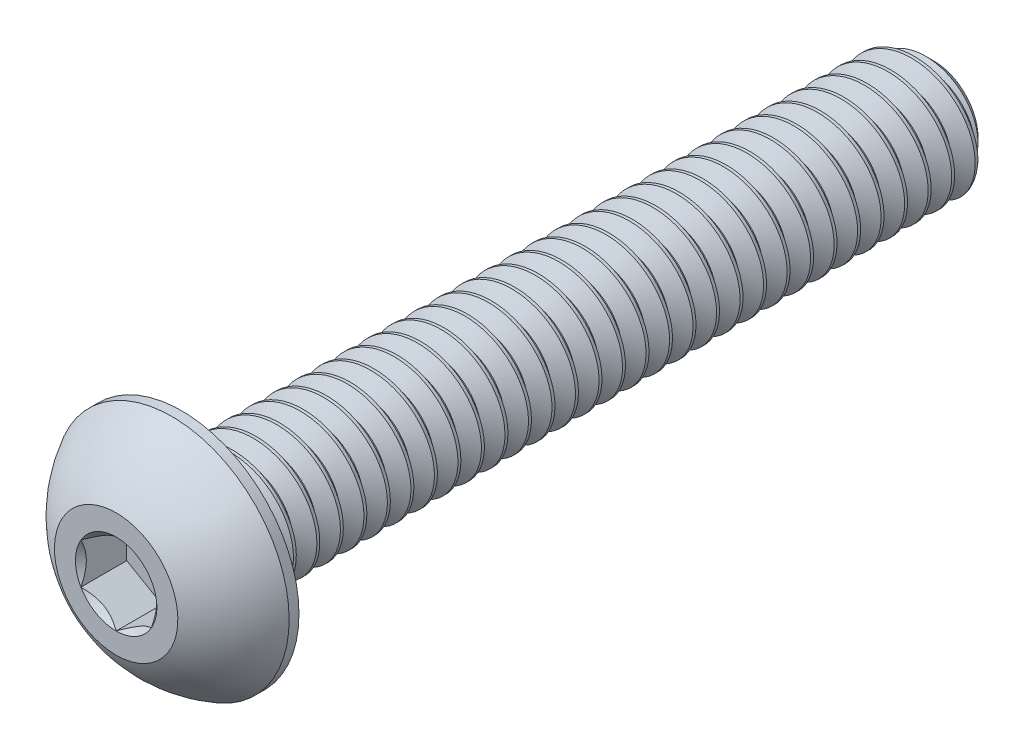
SolidWorks part; units mm, degrees
ref_plane "Front" through (0, 0, 0) normal (0, 0, 1) x (1, 0, 0)
ref_plane "Top" through (0, 0, 0) normal (0, 1, 0) x (1, 0, 0)
ref_plane "Right" through (0, 0, 0) normal (1, 0, 0) x (0, 0, -1)
sketch "Sketch1" plane through (0, 0, 0) normal (1, 0, 0) x (0, 0, -1)
  line L2 (2.2098, 2.0828) -> (27.6098, 2.0828)
  line L3 (27.6098, 2.0828) -> (27.6098, 0)
  line L4 (27.6098, 0) -> (2.2098, 0)
  line L6 (1.8783, 3.9624) -> (2.2098, 3.9624) construction
  line L7 (27.6098, 2.0828) -> (27.6098, -2.0828) construction
  line L8 (0, 0) -> (2.2098, 0) construction
  line L9 (2.2098, 3.9624) -> (2.2098, -3.9624) construction
  line L11 (2.2098, 2.0828) -> (2.2098, 0)
  line L13 (0, 1.1906) -> (0, -1.1906) construction
  line L14 (0, 1.1906) -> (0, 2.0828) construction
  arc A3 (0, 2.0828) -> (1.8783, 3.9624) centre (3.9638, 0) cw construction
  dimension "D1" = 0.3315
  dimension "Head Ht" = 2.2098
  dimension "Head Dia" = 7.9248
  dimension "Dia" = 4.1656
  dimension "Lg" = 25.4
  dimension "Hex" = 2.3813
revolve "Revolve1" add sketch "Sketch1" angle 360 mid plane about L4
sketch "Sketch3" plane through (0, 0, -27.6098) normal (0, 0, -1) x (-1, 0, 0)
  circle A0 centre (0, 0) radius 2.0828
curve "Helix/Spiral1" pitch 0.7937 height 27.6098 turns 34.784
sketch "Sketch2" plane through (0, 0, 0) normal (1, 0, 0) x (0, 0, -1)
  line L0 (27.6098, 2.0828) -> (28.3043, 2.0828)
  line L1 (28.3043, 2.0828) -> (28.0067, 1.5672)
  line L2 (28.0067, 1.5672) -> (27.9075, 1.5672)
  line L3 (27.9075, 1.5672) -> (27.6098, 2.0828)
  line L4 (27.7586, 1.825) -> (28.1555, 1.825) construction
  dimension "D1" = 60
  dimension "D2" = 0.0992
  dimension "D3" = 0.3969
chamfer "Chamfer1" distance 0.5953 angle 45 1 edges at (0, 2.0828, -27.6098)
sweep "Cut-Sweep1" cut profiles "Sketch2" path "Helix/Spiral1"
sketch "Sketch7" plane through (0, 0, 0) normal (1, 0, 0) x (0, 0, -1)
  line L6 (1.8783, 3.9624) -> (2.2098, 3.9624) construction
  line L8 (0, 0) -> (2.2098, 0) construction
  line L11 (2.2098, 3.9624) -> (2.2098, -3.9624) construction
  line L12 (1.8783, 3.9624) -> (2.2098, 3.9624)
  line L13 (0, 0) -> (2.2098, 0)
  line L14 (0, 1.1906) -> (0, -1.1906) construction
  line L15 (2.2098, 3.9624) -> (2.2098, 0)
  line L16 (0, 2.0828) -> (0, 0)
  arc A2 (1.8783, 3.9624) -> (0, 2.0828) centre (3.9638, 0) ccw construction
  arc A3 (1.8783, 3.9624) -> (0, 2.0828) centre (3.9638, 0) ccw
revolve "Revolve2" add sketch "Sketch7" angle 360 mid plane about L13
sketch "Sketch5" plane through (0, 0, 0) normal (0, 0, 1) x (1, 0, 0)
  line L1 (1.1906, -0.6874) -> (1.1906, 0.6874)
  line L2 (1.1906, 0.6874) -> (0, 1.3748)
  line L3 (0, 1.3748) -> (-1.1906, 0.6874)
  line L4 (-1.1906, 0.6874) -> (-1.1906, -0.6874)
  line L5 (-1.1906, -0.6874) -> (0, -1.3748)
  line L6 (0, -1.3748) -> (1.1906, -0.6874)
  circle A0 centre (0, 0) radius 1.1906 construction
extrude "Cut-Extrude2" cut sketch "Sketch5" against normal blind 1.5469
sketch "Sketch6" plane through (0, 0, 0) normal (0, 0, 1) x (1, 0, 0)
  circle A0 centre (0, 0) radius 1.3748
extrude "Cut-Extrude3" cut sketch "Sketch6" against normal blind 1.5469 draft 45
sketch "Sketch9" [suppressed] plane through (0, 0, -1.8542) normal (0, 0, 1) x (1, 0, 0)
  circle A2 centre (0, 0) radius 1.7526
extrude "Boss-Extrude2" [suppressed] add sketch "Sketch9" against normal offset from surface (19.05 mm away) 22.225
sketch "Sketch10" plane through (0, 0, 0) normal (1, 0, 0) x (0, 0, -1)
  line L0 (27.6098, 2.0828) -> (27.6098, -2.0828) construction
  point P0 (26.4192, -2.0828)
  dimension "D1" = 1.1906
equation "\"D3@Helix/Spiral1\" = \"Lg@Sketch1\" + \"Head Ht@Sketch1\""
equation "\"D2@Sketch2\" = \"D4@Helix/Spiral1\" * .125"
equation "\"D3@Sketch2\" = \"D4@Helix/Spiral1\" * .5"
equation "\"D1@Chamfer1\" = \"D4@Helix/Spiral1\" * .75"
equation "\"D1@Cut-Extrude2\" = \"Head Ht@Sketch1\" * .7"
equation "\"D1@Sketch1\" = \"Head Ht@Sketch1\" * .15"
equation "\"D1@Sketch10\" = \"D4@Helix/Spiral1\" * 1.5"
equation "\"D1@Cut-Extrude3\" = \"D1@Cut-Extrude2\""
